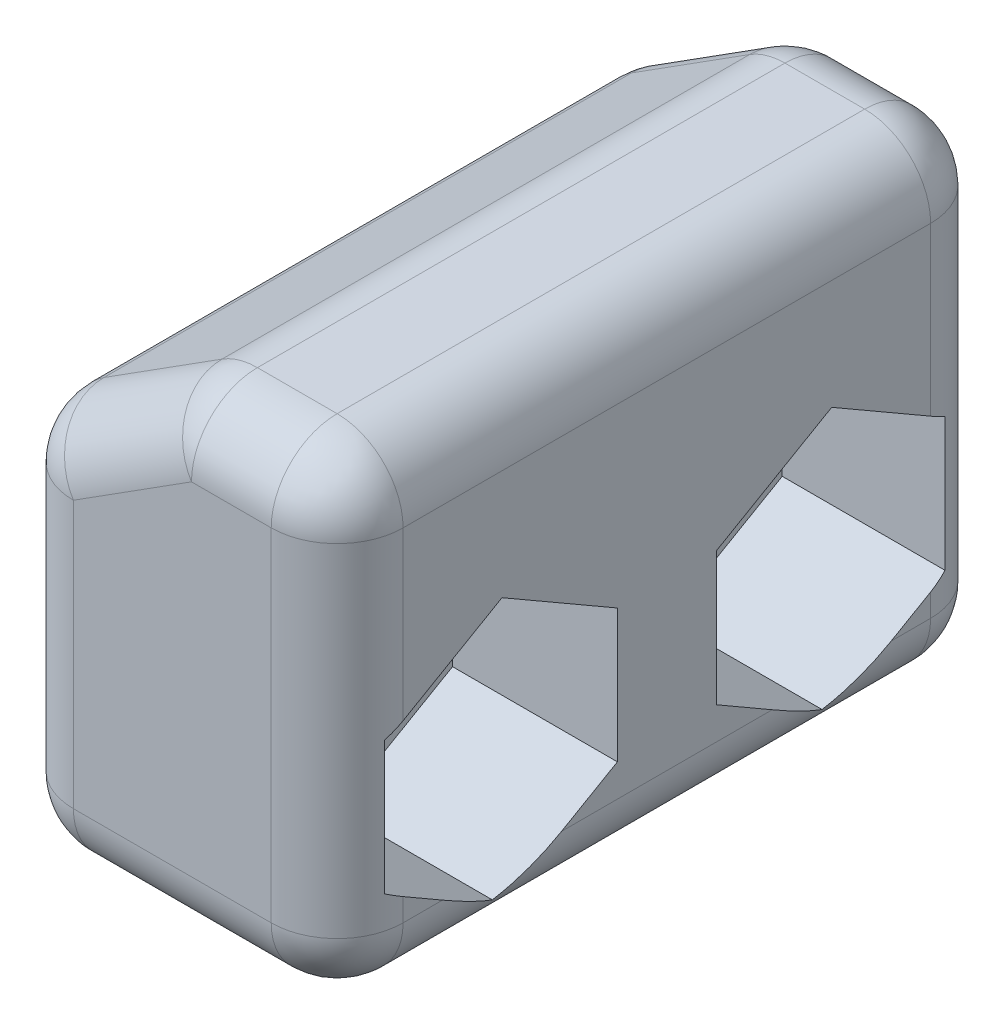
SolidWorks part; units mm, degrees
ref_plane "Front Plane" through (0, 0, 0) normal (0, 0, 1) x (1, 0, 0)
ref_plane "Top Plane" through (0, 0, 0) normal (0, 1, 0) x (1, 0, 0)
ref_plane "Right Plane" through (0, 0, 0) normal (1, 0, 0) x (0, 0, -1)
sketch "Sketch3" plane through (0, 0, 0) normal (0, 0, 1) x (1, 0, 0)
  line L0 (0, 14.224) -> (6.35, 18.2562)
  line L1 (6.35, 18.2562) -> (12.7, 18.2563)
  line L2 (12.7, 18.2563) -> (12.7, 0)
  line L3 (12.7, 0) -> (0, 0)
  line L4 (0, 0) -> (0, 14.224)
  dimension "D1" = 18.2562
  dimension "D2" = 6.35
  dimension "D3" = 6.35
  dimension "D4" = 14.224
extrude "Boss-Extrude1" add sketch "Sketch3" along normal blind 25.4
sketch "Sketch4" plane through (0, 0, 0) normal (-1, 0, 0) x (0, 0, 1)
  line L0 (25.4, 0) -> (0, 0) construction
  line L1 (6.35, 6.35) -> (0, 6.35) construction
  line L2 (0, 14.224) -> (0, 0) construction
  line L3 (19.05, 6.35) -> (25.4, 6.35) construction
  line L4 (25.4, 14.224) -> (25.4, 0) construction
  circle A0 centre (6.35, 6.35) radius 2.159
  circle A1 centre (19.05, 6.35) radius 2.159
  dimension "D1" = 6.35
  dimension "D2" = 12.7
  dimension "D3" = 4.318
extrude "Cut-Extrude1" cut sketch "Sketch4" against normal through all
sketch "Sketch6" plane through (12.7, 0, 0) normal (1, 0, 0) x (0, 0, -1)
  line L0 (-25.4, 0) -> (-25.4, 18.2562) construction
  line L1 (-14.605, 8.9163) -> (-19.05, 11.4826)
  line L2 (-19.05, 11.4826) -> (-23.495, 8.9163)
  line L3 (-23.495, 8.9163) -> (-23.495, 3.7837)
  line L4 (-23.495, 3.7837) -> (-19.05, 1.2174)
  line L5 (-19.05, 1.2174) -> (-14.605, 3.7837)
  line L6 (-14.605, 3.7837) -> (-14.605, 8.9163)
  line L8 (-1.905, 3.7837) -> (-1.905, 8.9163)
  line L9 (-1.905, 8.9163) -> (-6.35, 11.4826)
  line L10 (-6.35, 11.4826) -> (-10.795, 8.9163)
  line L11 (-10.795, 8.9163) -> (-10.795, 3.7837)
  line L12 (-10.795, 3.7837) -> (-6.35, 1.2174)
  line L13 (-6.35, 1.2174) -> (-1.905, 3.7837)
  circle A0 centre (-19.05, 6.35) radius 4.445 construction
  circle A1 centre (-6.35, 6.35) radius 4.445 construction
  dimension "D1" = 8.89
  dimension "D2" = 8.89
extrude "Cut-Extrude2" cut sketch "Sketch6" against normal blind 6.35
fillet "Fillet1" radius 2.54 15 edges at (0, 0, 12.7) (12.7, 0, 12.7) (12.7, 18.2563, 12.7) (6.35, 18.2562, 12.7) (3.175, 16.2401, 25.4) (9.525, 18.2563, 25.4) (12.7, 9.1281, 25.4) (6.35, 0, 25.4) (0, 7.112, 25.4) (6.35, 0, 0) (12.7, 9.1281, 0) (9.525, 18.2563, 0) (3.175, 16.2401, 0) (0, 7.112, 0) (0, 14.224, 12.7)
